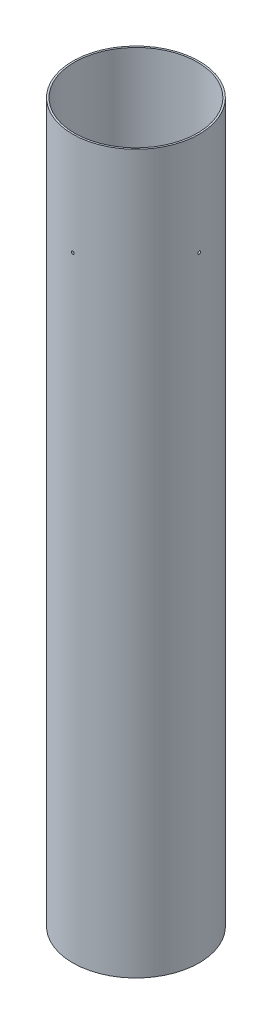
SolidWorks part; units mm, degrees
ref_plane "Front Plane" through (0, 0, 0) normal (0, 0, 1) x (1, 0, 0)
ref_plane "Top Plane" through (0, 0, 0) normal (0, 1, 0) x (1, 0, 0)
ref_plane "Right Plane" through (0, 0, 0) normal (1, 0, 0) x (0, 0, -1)
sketch "Sketch1" plane through (0, 0, 0) normal (0, 1, 0) x (1, 0, 0)
  circle A0 centre (0, 0) radius 76.2
  circle A1 centre (0, 0) radius 78.359
  dimension "D1" = 156.718
  dimension "D2" = 152.4
extrude "Boss-Extrude1" add sketch "Sketch1" along normal blind 889
ref_axis "Axis1" through (0, 889, 0) along (0, -1, 0)
sketch "Sketch3" plane through (0, 0, 0) normal (0, 0, 1) x (1, 0, 0)
  line L0 (0, 762) -> (0, 889) construction
  line L1 (78.359, 889) -> (-78.359, 889) construction
  circle A0 centre (0, 762) radius 1.75
  dimension "D2" = 3.5
  dimension "D1" = 127
extrude "Cut-Extrude1" cut sketch "Sketch3" against normal through all
pattern_circular "CirPattern1" count 4 over 360 about axis through (0, 889, 0) along (0, -1, 0) of "Cut-Extrude1"
equation "\"FWD_Tube_Length\"= 35in"
equation "\"D1@Boss-Extrude1\"=\"FWD_Tube_Length\""
equation "\"BKHD_Screw_Diam\"= 3.5mm"
equation "\"Screw_From_Top\"= 5in"
equation "\"D2@Sketch3\"=\"BKHD_Screw_Diam\""
equation "\"D1@Sketch3\"=\"Screw_From_Top\""
